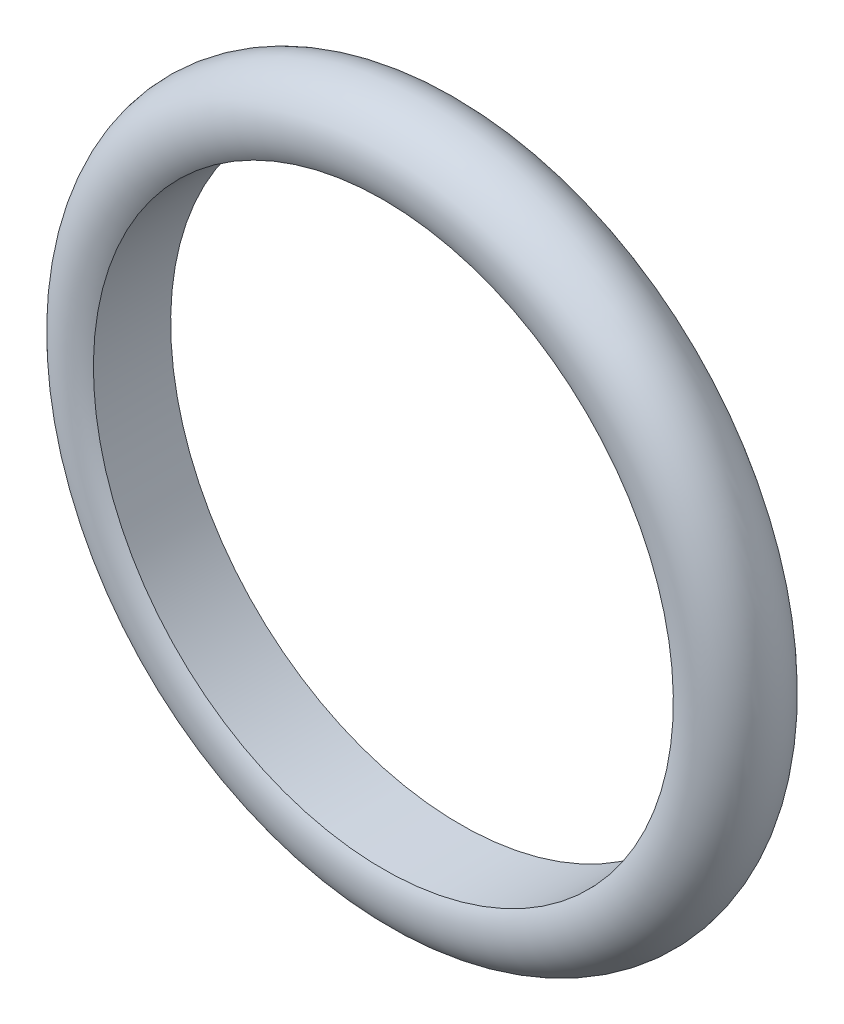
SolidWorks part; units mm, degrees
ref_plane "Front Plane" through (0, 0, 0) normal (0, 0, 1) x (1, 0, 0)
ref_plane "Top Plane" through (0, 0, 0) normal (0, 1, 0) x (1, 0, 0)
ref_plane "Right Plane" through (0, 0, 0) normal (1, 0, 0) x (0, 0, -1)
sketch "Sketch1" plane through (0, 0, 0) normal (0, 0, 1) x (1, 0, 0)
  circle A0 centre (0, 0) radius 35
  dimension "D1" = 70
sketch "Sketch2" plane through (0, 0, 0) normal (1, 0, 0) x (0, 0, -1)
  line L2 (4.3301, 32.5) -> (-4.3301, 32.5)
  arc A0 (4.3301, 32.5) -> (-4.3301, 32.5) centre (0, 35) ccw
  arc A1 (4.3301, 32.5) -> (-4.3301, 32.5) centre (0, 30) ccw construction
  dimension "D1" = 10
sweep "Sweep1" add profiles "Sketch2" path "Sketch1"
